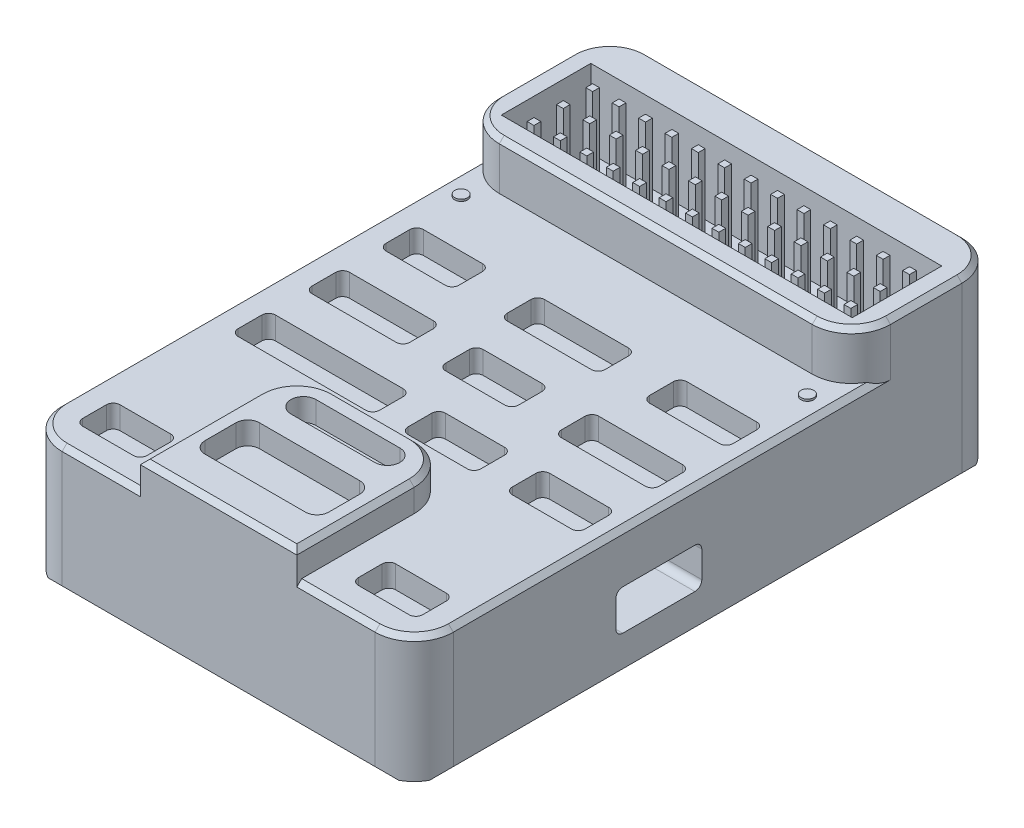
SolidWorks part; units mm, degrees
ref_plane "前视基准面" through (0, 0, 0) normal (0, 0, 1) x (1, 0, 0)
ref_plane "上视基准面" through (0, 0, 0) normal (0, 1, 0) x (1, 0, 0)
ref_plane "右视基准面" through (0, 0, 0) normal (1, 0, 0) x (0, 0, -1)
other "Configuration Table"
sketch "草图1" plane through (0, 0, 0) normal (0, 1, 0) x (1, 0, 0)
  line L0 (0, 0) -> (0, 21.7464) construction
  line L1 (20, 0) -> (-20, 0)
  line L2 (-20, 0) -> (-20, 60)
  line L3 (-20, 60) -> (20, 60)
  line L4 (20, 0) -> (20, 60)
  point P9 (0, 0)
  point P10 (0, 60)
  dimension "D1" = 40
  dimension "D2" = 60
extrude "凸台-拉伸1" add sketch "草图1" along normal blind 17.8
sketch "草图2" plane through (-20, 0, 0) normal (-1, 0, 0) x (0, 0, 1)
  line L0 (-40.8529, 6.1321) -> (-34.8554, 6.1321) construction
  line L1 (-40.8529, 7.8603) -> (-34.8554, 7.8603)
  line L2 (-40.8529, 4.404) -> (-34.8554, 4.404)
  line L3 (-40.8529, 6.1321) -> (-34.8554, 6.1321) construction
  line L4 (-29.4054, 7.757) -> (-20.6215, 7.757)
  line L5 (-29.4054, 7.757) -> (-29.4054, 3.6505)
  line L6 (-29.4054, 3.6505) -> (-20.6215, 3.6505)
  line L7 (-20.6215, 7.757) -> (-20.6215, 3.6505)
  line L8 (-40.8529, 7.3673) -> (-34.8554, 7.3673)
  line L9 (-40.8529, 4.897) -> (-34.8554, 4.897)
  line L10 (-44.7, 17.8) -> (-44.7, 12.9)
  line L11 (-44.7, 12.9) -> (0, 12.9)
  line L12 (0, 17.8) -> (0, 0) construction
  line L14 (-60, 0) -> (0, 0)
  line L15 (0, 0) -> (0, 17.8)
  line L16 (0, 17.8) -> (-60, 17.8)
  line L17 (-60, 17.8) -> (-60, 0)
  line L18 (-60, 0) -> (0, 0)
  line L19 (0, 0) -> (0, 17.8)
  line L20 (0, 17.8) -> (-60, 17.8)
  line L21 (-60, 17.8) -> (-60, 0)
  arc A0 (-40.8529, 7.8603) -> (-40.8529, 4.404) centre (-40.8529, 6.1321) ccw
  arc A1 (-34.8554, 4.404) -> (-34.8554, 7.8603) centre (-34.8554, 6.1321) ccw
  arc A2 (-40.8529, 7.3673) -> (-40.8529, 4.897) centre (-40.8529, 6.1321) ccw
  arc A3 (-34.8554, 4.897) -> (-34.8554, 7.3673) centre (-34.8554, 6.1321) ccw
  point P2 (-37.8541, 6.1321)
  point P9 (-37.8541, 6.1321)
  point P24 (0, 13.395)
  point P28 (0, 0)
  point P29 (-40.8529, 7.3673)
  line M2 (0, 0) -> (0, 17.8)
  line M3 (0, 17.8) -> (-60, 17.8)
  dimension "D1" = 0
  dimension "D2" = 15.3
  dimension "D3" = 4.9
extrude "切除-拉伸1" cut sketch "草图2" against normal through all contours L10 L11 M2 M3 region at (-20, 15.35, -22.35)
extrude "切除-拉伸2" cut sketch "草图2<3>" against normal blind 5 contours L7 L4 L5 L6 region at (-20, 5.7038, -25.0134)
sketch "草图2<3>" plane through (-20, 0, 0) normal (-1, 0, 0) x (0, 0, 1) same geometry as "草图2"
extrude "切除-拉伸3" cut sketch "草图2<4>" against normal blind 1.5 contours L2 A1 L1 A0 A3 L9 A2 L8 region at (-20, 7.7596, -37.8541)
sketch "草图2<4>" plane through (-20, 0, 0) normal (-1, 0, 0) x (0, 0, 1) same geometry as "草图2"
extrude "切除-拉伸4" cut sketch "草图2<5>" against normal blind 4 contours L9 A3 L8 A2 region at (-20, 6.1321, -37.8541)
sketch "草图2<5>" plane through (-20, 0, 0) normal (-1, 0, 0) x (0, 0, 1) same geometry as "草图2"
sketch "草图4" plane through (0, 0, 0) normal (0, 0, 1) x (1, 0, 0)
  line L0 (0, 12.9) -> (0, 0) construction
  line L1 (-8, 12.9) -> (-8, 15.734)
  line L2 (-8, 15.734) -> (8, 15.734)
  line L3 (8, 12.9) -> (8, 15.734)
  line L4 (20, 0) -> (20, 12.9)
  line L5 (20, 12.9) -> (-20, 12.9)
  line L6 (-20, 12.9) -> (-20, 0)
  line L7 (-20, 0) -> (20, 0)
  line L8 (20, 0) -> (20, 12.9)
  line L9 (20, 12.9) -> (-20, 12.9)
  line L10 (-20, 12.9) -> (-20, 0)
  line L11 (-20, 0) -> (20, 0)
  point P11 (0, 15.734)
  line M6 (20, 12.9) -> (-20, 12.9)
  dimension "D2" = 8
  dimension "D3" = 2.834
  dimension "D1" = 0
extrude "凸台-拉伸2" add sketch "草图4" against normal blind 16 contours L3 L2 L1 L9 M6 region at (0, 14.317, 0)
sketch "草图5" plane through (0, 12.9, 0) normal (0, 1, 0) x (1, 0, 0)
  line L0 (0, 44.7) -> (0, 16) construction
  line L1 (-17.3827, 37.6277) -> (-9.9418, 37.6277)
  line L2 (-17.3827, 37.6277) -> (-17.3827, 33.8126)
  line L3 (-17.3827, 33.8126) -> (-9.9418, 33.8126)
  line L4 (-9.9418, 37.6277) -> (-9.9418, 33.8126)
  line L5 (-4.9969, 37.6277) -> (4.9969, 37.6277)
  line L6 (-4.9969, 37.6277) -> (-4.9969, 33.8126)
  line L7 (-4.9969, 33.8126) -> (4.9969, 33.8126)
  line L8 (4.9969, 37.6277) -> (4.9969, 33.8126)
  line L9 (9.5637, 37.6277) -> (18.0938, 37.6277)
  line L10 (9.5637, 37.6277) -> (9.5637, 33.8126)
  line L11 (9.5637, 33.8126) -> (18.0938, 33.8126)
  line L12 (18.0938, 37.6277) -> (18.0938, 33.8126)
  line L13 (-17.3827, 30.0626) -> (-7.3959, 30.0626)
  line L14 (-17.3827, 30.0626) -> (-17.3827, 26.2476)
  line L15 (-17.3827, 26.2476) -> (-7.3959, 26.2476)
  line L16 (-7.3959, 30.0626) -> (-7.3959, 26.2476)
  line L17 (-3.7204, 30.0626) -> (3.7204, 30.0626)
  line L18 (-3.7204, 30.0626) -> (-3.7204, 26.2476)
  line L19 (-3.7204, 26.2476) -> (3.7204, 26.2476)
  line L20 (3.7204, 30.0626) -> (3.7204, 26.2476)
  line L21 (8.1071, 30.0626) -> (18.0938, 30.0626)
  line L22 (8.1071, 30.0626) -> (8.1071, 26.2476)
  line L23 (8.1071, 26.2476) -> (18.0938, 26.2476)
  line L24 (18.0938, 30.0626) -> (18.0938, 26.2476)
  line L25 (-17.3827, 22.4976) -> (-2.924, 22.4976)
  line L26 (-17.3827, 22.4976) -> (-17.3827, 18.6825)
  line L27 (-17.3827, 18.6825) -> (-2.924, 18.6825)
  line L28 (-2.924, 22.4976) -> (-2.924, 18.6825)
  line L29 (0, 22.4976) -> (7.4409, 22.4976)
  line L30 (0, 22.4976) -> (0, 18.6825)
  line L31 (0, 18.6825) -> (7.4409, 18.6825)
  line L32 (7.4409, 22.4976) -> (7.4409, 18.6825)
  line L33 (10.653, 22.4976) -> (18.0938, 22.4976)
  line L34 (10.653, 22.4976) -> (10.653, 18.6825)
  line L35 (10.653, 18.6825) -> (18.0938, 18.6825)
  line L36 (18.0938, 22.4976) -> (18.0938, 18.6825)
  line L37 (10.8069, 6.6036) -> (10.8069, 2.7885)
  line L44 (-8, 0) -> (-8, 16)
  line L45 (-8, 16) -> (8, 16)
  line L46 (8, 16) -> (8, 0)
  line L47 (8, 0) -> (20, 0)
  line L48 (20, 0) -> (20, 44.7)
  line L49 (20, 44.7) -> (-20, 44.7)
  line L50 (-20, 44.7) -> (-20, 0)
  line L51 (-20, 0) -> (-8, 0)
  line L52 (-8, 0) -> (-8, 16)
  line L53 (-8, 16) -> (8, 16)
  line L54 (8, 16) -> (8, 0)
  line L55 (8, 0) -> (20, 0)
  line L56 (20, 0) -> (20, 44.7)
  line L57 (20, 44.7) -> (-20, 44.7)
  line L58 (-20, 44.7) -> (-20, 0)
  line L59 (-20, 0) -> (-8, 0)
  line L62 (-17.3827, 6.6036) -> (-10.8069, 6.6036)
  line L63 (-17.3827, 6.6036) -> (-17.3827, 2.7885)
  line L64 (-17.3827, 2.7885) -> (-10.8069, 2.7885)
  line L65 (-10.8069, 6.6036) -> (-10.8069, 2.7885)
  line L66 (17.3827, 2.7885) -> (10.8069, 2.7885)
  line L67 (17.3827, 6.6036) -> (17.3827, 2.7885)
  line L68 (17.3827, 6.6036) -> (10.8069, 6.6036)
  dimension "D2" = 7.0723
  dimension "D3" = 7.4409
  dimension "D4" = 3.8151
  dimension "D5" = 2.6173
  dimension "D6" = 9.9938
  dimension "D7" = 4.5668
  dimension "D8" = 8.5302
  dimension "D9" = 9.9868
  dimension "D10" = 3.75
  dimension "D11" = 3.75
  dimension "D12" = 14.4587
  dimension "D13" = 2.7885
  dimension "D14" = 2.6173
  dimension "D15" = 6.5757
  dimension "D1" = 0
extrude "切除-拉伸5" cut sketch "草图5" against normal blind 2.3 contours L4 L1 L2 L3 | L0 L5 L6 L7 | L5 L0 L7 L8 | L12 L9 L10 L11 | L17 L0 L19 L20 | L0 L17 L18 L19 | L24 L21 L22 L23 | L36 L33 L34 L35 | L32 L29 L30 L31 | L28 L25 L26 L27 | L65 L62 L63 L64 | L67 L68 L37 L66 | L16 L13 L14 L15 | L15 L16 L13 L14 region at (3.7204, 12.9, -20.59) region at (-1.8602, 12.9, -28.1551) region at (1.8602, 12.9, -28.1551) region at (-2.4984, 12.9, -35.7202) region at (2.4984, 12.9, -35.7202) region at (-13.6622, 12.9, -35.7202) region at (13.8288, 12.9, -35.7202) region at (-12.3893, 12.9, -28.1551) region at (13.1005, 12.9, -28.1551) region at (-10.1533, 12.9, -20.59) region at (14.3734, 12.9, -20.59) region at (14.0948, 12.9, -4.6961) region at (-14.0948, 12.9, -4.6961)
sketch "草图6" plane through (0, 15.734, 0) normal (0, 1, 0) x (1, 0, 0)
  line L0 (0, 16) -> (0, 0) construction
  line L1 (8, 16) -> (-8, 16) construction
  line L2 (-4.2909, 12.9668) -> (4.2909, 12.9668) construction
  line L3 (-4.2909, 14.2476) -> (4.2909, 14.2476)
  line L4 (-4.2909, 11.6859) -> (4.2909, 11.6859)
  line L5 (-8, 0) -> (8, 0) construction
  line L6 (-6.3278, 9.3041) -> (6.3278, 9.3041)
  line L7 (-6.3278, 9.3041) -> (-6.3278, 3.738)
  line L8 (-6.3278, 3.738) -> (6.3278, 3.738)
  line L9 (6.3278, 9.3041) -> (6.3278, 3.738)
  arc A0 (-4.2909, 14.2476) -> (-4.2909, 11.6859) centre (-4.2909, 12.9668) ccw
  arc A1 (4.2909, 11.6859) -> (4.2909, 14.2476) centre (4.2909, 12.9668) ccw
  point P7 (0, 12.9668)
  point P16 (0, 0)
  dimension "D1" = 1.2809
  dimension "D2" = 8.5817
  dimension "D3" = 3.0332
  dimension "D4" = 6.3278
  dimension "D5" = 5.5661
  dimension "D6" = 3.738
extrude "切除-拉伸6" cut sketch "草图6" against normal blind 2.3
mirror "镜向1" about plane through (0, 0, 0) normal (1, 0, 0) of "切除-拉伸2"
chamfer "倒角1" distance 0.5 4 edges at (0, 0, -60) (-20, 0, -30) (0, 0, 0) (20, 0, -30)
fillet "圆角1" radius 4 4 edges at (-20, 9.15, -60) (20, 9.15, -60) (20, 6.7, 0) (-20, 6.7, 0)
fillet "圆角2" radius 4 2 edges at (8, 14.317, -16) (-8, 14.317, -16)
chamfer "倒角10" distance 0.5 angle 45 6 edges at (-8, 15.734, -6) (-6.8284, 15.734, -14.8284) (0, 15.734, -16) (8, 15.734, -6) (6.8284, 15.734, -14.8284) (0, 15.734, 0)
chamfer "倒角11" distance 0.5 6 edges at (12, 12.9, 0) (18.8284, 12.9, -1.1716) (20, 12.9, -24.35) (-12, 12.9, 0) (-18.8284, 12.9, -1.1716) (-20, 12.9, -24.35)
fillet "圆角3" radius 4 2 edges at (20, 15.1, -44.7) (-20, 15.1, -44.7)
chamfer "倒角13" distance 0.5 8 edges at (-18.8284, 17.8, -45.8716) (-20, 17.8, -52.35) (-18.8284, 17.8, -58.8284) (0, 17.8, -60) (18.8284, 17.8, -58.8284) (20, 17.8, -52.35) (18.8284, 17.8, -45.8716) (0, 17.8, -44.7)
sketch "草图9" plane through (0, 17.8, 0) normal (0, 1, 0) x (1, 0, 0)
  line L0 (0, 59.5) -> (0, 45.2) construction
  line L2 (-17.9426, 56) -> (17.9426, 56)
  line L3 (-17.9426, 56) -> (-17.9426, 46.8497)
  line L4 (-19.5, 56) -> (-19.5, 48.7)
  line L5 (-16, 45.2) -> (16, 45.2)
  line L6 (19.5, 48.7) -> (19.5, 56)
  line L7 (16, 59.5) -> (-16, 59.5)
  line L8 (-19.5, 56) -> (-19.5, 48.7)
  line L9 (-16, 45.2) -> (16, 45.2)
  line L10 (19.5, 48.7) -> (19.5, 56)
  line L11 (16, 59.5) -> (-16, 59.5)
  line L12 (-17.9426, 46.8497) -> (17.9426, 46.8497)
  line L13 (17.9426, 56) -> (17.9426, 46.8497)
  arc A4 (-19.5, 48.7) -> (-16, 45.2) centre (-16, 48.7) ccw
  arc A5 (16, 45.2) -> (19.5, 48.7) centre (16, 48.7) ccw
  arc A6 (19.5, 56) -> (16, 59.5) centre (16, 56) ccw
  arc A7 (-16, 59.5) -> (-19.5, 56) centre (-16, 56) ccw
  arc A8 (-19.5, 48.7) -> (-16, 45.2) centre (-16, 48.7) ccw
  arc A9 (16, 45.2) -> (19.5, 48.7) centre (16, 48.7) ccw
  arc A10 (19.5, 56) -> (16, 59.5) centre (16, 56) ccw
  arc A11 (-16, 59.5) -> (-19.5, 56) centre (-16, 56) ccw
  dimension "D2" = 1.6497
  dimension "D3" = 17.9426
  dimension "D4" = 9.1503
  dimension "D1" = 0
extrude "切除-拉伸7" cut sketch "草图9" against normal blind 8 contours L0 L2 L3 L12 | L2 L0 L12 L13 region at (8.9713, 17.8, -51.4249) region at (-8.9713, 17.8, -51.4249)
sketch "草图10" plane through (0, 9.8, 0) normal (0, 1, 0) x (1, 0, 0)
  line L0 (0, 56) -> (0, 46.8497) construction
  line L1 (2.35, 54.7959) -> (3.05, 54.7959)
  line L2 (-0.35, 54.7959) -> (0.35, 54.7959)
  line L3 (-0.35, 54.7959) -> (-0.35, 54.0959)
  line L4 (-17.9426, 46.8497) -> (17.9426, 46.8497)
  line L5 (17.9426, 46.8497) -> (17.9426, 56)
  line L6 (17.9426, 56) -> (-17.9426, 56)
  line L7 (-17.9426, 56) -> (-17.9426, 46.8497)
  line L8 (-17.9426, 46.8497) -> (17.9426, 46.8497)
  line L9 (17.9426, 46.8497) -> (17.9426, 56)
  line L10 (17.9426, 56) -> (-17.9426, 56)
  line L11 (-17.9426, 56) -> (-17.9426, 46.8497)
  line L12 (-0.35, 54.0959) -> (0.35, 54.0959)
  line L13 (0.35, 54.7959) -> (0.35, 54.0959)
  line L14 (3.05, 54.7959) -> (3.05, 54.0959)
  line L15 (2.35, 54.0959) -> (3.05, 54.0959)
  line L16 (2.35, 54.7959) -> (2.35, 54.0959)
  line L17 (5.05, 54.7959) -> (5.75, 54.7959)
  line L18 (5.75, 54.7959) -> (5.75, 54.0959)
  line L19 (5.05, 54.0959) -> (5.75, 54.0959)
  line L20 (5.05, 54.7959) -> (5.05, 54.0959)
  line L21 (7.75, 54.7959) -> (8.45, 54.7959)
  line L22 (8.45, 54.7959) -> (8.45, 54.0959)
  line L23 (7.75, 54.0959) -> (8.45, 54.0959)
  line L24 (7.75, 54.7959) -> (7.75, 54.0959)
  line L25 (10.45, 54.7959) -> (11.15, 54.7959)
  line L26 (11.15, 54.7959) -> (11.15, 54.0959)
  line L27 (10.45, 54.0959) -> (11.15, 54.0959)
  line L28 (10.45, 54.7959) -> (10.45, 54.0959)
  line L29 (13.15, 54.7959) -> (13.85, 54.7959)
  line L30 (13.85, 54.7959) -> (13.85, 54.0959)
  line L31 (13.15, 54.0959) -> (13.85, 54.0959)
  line L32 (13.15, 54.7959) -> (13.15, 54.0959)
  line L33 (15.85, 54.7959) -> (16.55, 54.7959)
  line L34 (16.55, 54.7959) -> (16.55, 54.0959)
  line L35 (15.85, 54.0959) -> (16.55, 54.0959)
  line L36 (15.85, 54.7959) -> (15.85, 54.0959)
  line L37 (2.35, 51.7959) -> (3.05, 51.7959)
  line L38 (3.05, 51.7959) -> (3.05, 51.0959)
  line L39 (2.35, 51.0959) -> (3.05, 51.0959)
  line L40 (2.35, 51.7959) -> (2.35, 51.0959)
  line L41 (5.05, 51.7959) -> (5.75, 51.7959)
  line L42 (5.75, 51.7959) -> (5.75, 51.0959)
  line L43 (5.05, 51.0959) -> (5.75, 51.0959)
  line L44 (5.05, 51.7959) -> (5.05, 51.0959)
  line L45 (7.75, 51.7959) -> (8.45, 51.7959)
  line L46 (8.45, 51.7959) -> (8.45, 51.0959)
  line L47 (7.75, 51.0959) -> (8.45, 51.0959)
  line L48 (7.75, 51.7959) -> (7.75, 51.0959)
  line L49 (10.45, 51.7959) -> (11.15, 51.7959)
  line L50 (11.15, 51.7959) -> (11.15, 51.0959)
  line L51 (10.45, 51.0959) -> (11.15, 51.0959)
  line L52 (10.45, 51.7959) -> (10.45, 51.0959)
  line L53 (13.15, 51.7959) -> (13.85, 51.7959)
  line L54 (13.85, 51.7959) -> (13.85, 51.0959)
  line L55 (13.15, 51.0959) -> (13.85, 51.0959)
  line L56 (13.15, 51.7959) -> (13.15, 51.0959)
  line L57 (15.85, 51.7959) -> (16.55, 51.7959)
  line L58 (16.55, 51.7959) -> (16.55, 51.0959)
  line L59 (15.85, 51.0959) -> (16.55, 51.0959)
  line L60 (15.85, 51.7959) -> (15.85, 51.0959)
  line L61 (2.35, 48.7959) -> (3.05, 48.7959)
  line L62 (3.05, 48.7959) -> (3.05, 48.0959)
  line L63 (2.35, 48.0959) -> (3.05, 48.0959)
  line L64 (2.35, 48.7959) -> (2.35, 48.0959)
  line L65 (5.05, 48.7959) -> (5.75, 48.7959)
  line L66 (5.75, 48.7959) -> (5.75, 48.0959)
  line L67 (5.05, 48.0959) -> (5.75, 48.0959)
  line L68 (5.05, 48.7959) -> (5.05, 48.0959)
  line L69 (7.75, 48.7959) -> (8.45, 48.7959)
  line L70 (8.45, 48.7959) -> (8.45, 48.0959)
  line L71 (7.75, 48.0959) -> (8.45, 48.0959)
  line L72 (7.75, 48.7959) -> (7.75, 48.0959)
  line L73 (10.45, 48.7959) -> (11.15, 48.7959)
  line L74 (11.15, 48.7959) -> (11.15, 48.0959)
  line L75 (10.45, 48.0959) -> (11.15, 48.0959)
  line L76 (10.45, 48.7959) -> (10.45, 48.0959)
  line L77 (13.15, 48.7959) -> (13.85, 48.7959)
  line L78 (13.85, 48.7959) -> (13.85, 48.0959)
  line L79 (13.15, 48.0959) -> (13.85, 48.0959)
  line L80 (13.15, 48.7959) -> (13.15, 48.0959)
  line L81 (15.85, 48.7959) -> (16.55, 48.7959)
  line L82 (16.55, 48.7959) -> (16.55, 48.0959)
  line L83 (15.85, 48.0959) -> (16.55, 48.0959)
  line L84 (15.85, 48.7959) -> (15.85, 48.0959)
  line L85 (-0.35, 51.7959) -> (0.35, 51.7959)
  line L86 (0.35, 51.7959) -> (0.35, 51.0959)
  line L87 (-0.35, 51.0959) -> (0.35, 51.0959)
  line L88 (-0.35, 51.7959) -> (-0.35, 51.0959)
  line L89 (-0.35, 48.7959) -> (0.35, 48.7959)
  line L90 (0.35, 48.7959) -> (0.35, 48.0959)
  line L91 (-0.35, 48.0959) -> (0.35, 48.0959)
  line L92 (-0.35, 48.7959) -> (-0.35, 48.0959)
  line L93 (-15.85, 48.7959) -> (-15.85, 48.0959)
  line L94 (-15.85, 48.0959) -> (-16.55, 48.0959)
  line L95 (-16.55, 48.7959) -> (-16.55, 48.0959)
  line L96 (-15.85, 48.7959) -> (-16.55, 48.7959)
  line L97 (-13.15, 48.7959) -> (-13.15, 48.0959)
  line L98 (-13.15, 48.0959) -> (-13.85, 48.0959)
  line L99 (-13.85, 48.7959) -> (-13.85, 48.0959)
  line L100 (-13.15, 48.7959) -> (-13.85, 48.7959)
  line L101 (-10.45, 48.7959) -> (-10.45, 48.0959)
  line L102 (-10.45, 48.0959) -> (-11.15, 48.0959)
  line L103 (-11.15, 48.7959) -> (-11.15, 48.0959)
  line L104 (-10.45, 48.7959) -> (-11.15, 48.7959)
  line L105 (-7.75, 48.7959) -> (-7.75, 48.0959)
  line L106 (-7.75, 48.0959) -> (-8.45, 48.0959)
  line L107 (-8.45, 48.7959) -> (-8.45, 48.0959)
  line L108 (-7.75, 48.7959) -> (-8.45, 48.7959)
  line L109 (-5.05, 48.7959) -> (-5.05, 48.0959)
  line L110 (-5.05, 48.0959) -> (-5.75, 48.0959)
  line L111 (-5.75, 48.7959) -> (-5.75, 48.0959)
  line L112 (-5.05, 48.7959) -> (-5.75, 48.7959)
  line L113 (-2.35, 48.7959) -> (-2.35, 48.0959)
  line L114 (-2.35, 48.0959) -> (-3.05, 48.0959)
  line L115 (-3.05, 48.7959) -> (-3.05, 48.0959)
  line L116 (-2.35, 48.7959) -> (-3.05, 48.7959)
  line L117 (-15.85, 51.7959) -> (-15.85, 51.0959)
  line L118 (-15.85, 51.0959) -> (-16.55, 51.0959)
  line L119 (-16.55, 51.7959) -> (-16.55, 51.0959)
  line L120 (-15.85, 51.7959) -> (-16.55, 51.7959)
  line L121 (-13.15, 51.7959) -> (-13.15, 51.0959)
  line L122 (-13.15, 51.0959) -> (-13.85, 51.0959)
  line L123 (-13.85, 51.7959) -> (-13.85, 51.0959)
  line L124 (-13.15, 51.7959) -> (-13.85, 51.7959)
  line L125 (-10.45, 51.7959) -> (-10.45, 51.0959)
  line L126 (-10.45, 51.0959) -> (-11.15, 51.0959)
  line L127 (-11.15, 51.7959) -> (-11.15, 51.0959)
  line L128 (-10.45, 51.7959) -> (-11.15, 51.7959)
  line L129 (-7.75, 51.7959) -> (-7.75, 51.0959)
  line L130 (-7.75, 51.0959) -> (-8.45, 51.0959)
  line L131 (-8.45, 51.7959) -> (-8.45, 51.0959)
  line L132 (-7.75, 51.7959) -> (-8.45, 51.7959)
  line L133 (-5.05, 51.7959) -> (-5.05, 51.0959)
  line L134 (-5.05, 51.0959) -> (-5.75, 51.0959)
  line L135 (-5.75, 51.7959) -> (-5.75, 51.0959)
  line L136 (-5.05, 51.7959) -> (-5.75, 51.7959)
  line L137 (-2.35, 51.7959) -> (-2.35, 51.0959)
  line L138 (-2.35, 51.0959) -> (-3.05, 51.0959)
  line L139 (-3.05, 51.7959) -> (-3.05, 51.0959)
  line L140 (-2.35, 51.7959) -> (-3.05, 51.7959)
  line L141 (-15.85, 54.7959) -> (-15.85, 54.0959)
  line L142 (-15.85, 54.0959) -> (-16.55, 54.0959)
  line L143 (-16.55, 54.7959) -> (-16.55, 54.0959)
  line L144 (-15.85, 54.7959) -> (-16.55, 54.7959)
  line L145 (-13.15, 54.7959) -> (-13.15, 54.0959)
  line L146 (-13.15, 54.0959) -> (-13.85, 54.0959)
  line L147 (-13.85, 54.7959) -> (-13.85, 54.0959)
  line L148 (-13.15, 54.7959) -> (-13.85, 54.7959)
  line L149 (-10.45, 54.7959) -> (-10.45, 54.0959)
  line L150 (-10.45, 54.0959) -> (-11.15, 54.0959)
  line L151 (-11.15, 54.7959) -> (-11.15, 54.0959)
  line L152 (-10.45, 54.7959) -> (-11.15, 54.7959)
  line L153 (-7.75, 54.7959) -> (-7.75, 54.0959)
  line L154 (-7.75, 54.0959) -> (-8.45, 54.0959)
  line L155 (-8.45, 54.7959) -> (-8.45, 54.0959)
  line L156 (-7.75, 54.7959) -> (-8.45, 54.7959)
  line L157 (-5.05, 54.7959) -> (-5.05, 54.0959)
  line L158 (-5.05, 54.0959) -> (-5.75, 54.0959)
  line L159 (-5.75, 54.7959) -> (-5.75, 54.0959)
  line L160 (-5.05, 54.7959) -> (-5.75, 54.7959)
  line L161 (-2.35, 54.7959) -> (-2.35, 54.0959)
  line L162 (-2.35, 54.0959) -> (-3.05, 54.0959)
  line L163 (-3.05, 54.7959) -> (-3.05, 54.0959)
  line L164 (-2.35, 54.7959) -> (-3.05, 54.7959)
  dimension "D2" = 0.7
  dimension "D3" = 1.2041
  dimension "D1" = 0
  dimension "D4" = 7
  dimension "D5" = 3
extrude "凸台-拉伸5" add sketch "草图10" along normal blind 7.5 contours L141 L144 L143 L142 | L117 L120 L119 L118 | L93 L96 L95 L94 | L97 L100 L99 L98 | L121 L124 L123 L122 | L145 L148 L147 L146 | L149 L152 L151 L150 | L125 L128 L127 L126 | L101 L104 L103 L102 | L105 L108 L107 L106 | L109 L112 L111 L110 | L113 L116 L115 L114 | L137 L140 L139 L138 | L133 L136 L135 L134 | L129 L132 L131 L130 | L157 L160 L159 L158 | L161 L164 L163 L162 | L0 L2 L3 L12 | L2 L0 L12 L13 | L0 L85 L88 L87 | L85 L0 L87 L86 | L0 L89 L92 L91 | L89 L0 L91 L90 | L37 L40 L39 L38 | L1 L16 L15 L14 | L17 L20 L19 L18 | L41 L44 L43 L42 | L69 L72 L71 L70 | L45 L48 L47 L46 | L21 L24 L23 L22 | L25 L28 L27 L26 | L49 L52 L51 L50 | L73 L76 L75 L74 | L77 L80 L79 L78 | L53 L56 L55 L54 | L29 L32 L31 L30 | L33 L36 L35 L34 | L57 L60 L59 L58 | L81 L84 L83 L82 | L155 L154 L153 L156 | L64 L63 L62 L61 | L66 L67 L68 L65 region at (0.175, 9.8, -54.4459) region at (-0.175, 9.8, -54.4459) region at (0.175, 9.8, -51.4459) region at (-0.175, 9.8, -51.4459) region at (-0.175, 9.8, -48.4459) region at (0.175, 9.8, -48.4459) region at (2.7, 9.8, -54.4459) region at (5.4, 9.8, -54.4459) region at (8.1, 9.8, -54.4459) region at (10.8, 9.8, -54.4459) region at (13.5, 9.8, -54.4459) region at (16.2, 9.8, -54.4459) region at (2.7, 9.8, -51.4459) region at (5.4, 9.8, -51.4459) region at (8.1, 9.8, -51.4459) region at (10.8, 9.8, -51.4459) region at (13.5, 9.8, -51.4459) region at (16.2, 9.8, -51.4459) region at (8.1, 9.8, -48.4459) region at (10.8, 9.8, -48.4459) region at (13.5, 9.8, -48.4459) region at (16.2, 9.8, -48.4459) region at (-16.2, 9.8, -48.4459) region at (-13.5, 9.8, -48.4459) region at (-10.8, 9.8, -48.4459) region at (-8.1, 9.8, -48.4459) region at (-5.4, 9.8, -48.4459) region at (-2.7, 9.8, -48.4459) region at (-16.2, 9.8, -51.4459) region at (-13.5, 9.8, -51.4459) region at (-10.8, 9.8, -51.4459) region at (-8.1, 9.8, -51.4459) region at (-5.4, 9.8, -51.4459) region at (-2.7, 9.8, -51.4459) region at (-16.2, 9.8, -54.4459) region at (-13.5, 9.8, -54.4459) region at (-10.8, 9.8, -54.4459) region at (-5.4, 9.8, -54.4459) region at (-2.7, 9.8, -54.4459)
fillet "圆角5" radius 0.7 52 edges at (-17.5, 3.6505, -20.6215) (-17.5, 3.6505, -29.4054) (-17.5, 7.757, -20.6215) (-17.5, 7.757, -29.4054) (17.5, 3.6505, -20.6215) (17.5, 7.757, -29.4054) (17.5, 7.757, -20.6215) (17.5, 3.6505, -29.4054) (18.0938, 11.75, -33.8126) (4.9969, 11.75, -33.8126) (-9.9418, 11.75, -33.8126) (-7.3959, 11.75, -26.2476) (3.7204, 11.75, -26.2476) (18.0938, 11.75, -26.2476) (18.0938, 11.75, -18.6825) (7.4409, 11.75, -18.6825) (-2.924, 11.75, -18.6825) (-10.8069, 11.75, -2.7885) (17.3827, 11.75, -2.7885) (9.5637, 11.75, -33.8126) (8.1071, 11.75, -26.2476) (10.653, 11.75, -18.6825) (0, 11.75, -18.6825) (-3.7204, 11.75, -26.2476) (-4.9969, 11.75, -33.8126) (-17.3827, 11.75, -33.8126) (-17.3827, 11.75, -26.2476) (-17.3827, 11.75, -18.6825) (-17.3827, 11.75, -2.7885) (10.8069, 11.75, -2.7885) (9.5637, 11.75, -37.6277) (-4.9969, 11.75, -37.6277) (-17.3827, 11.75, -37.6277) (-17.3827, 11.75, -30.0626) (-3.7204, 11.75, -30.0626) (8.1071, 11.75, -30.0626) (10.653, 11.75, -22.4976) (0, 11.75, -22.4976) (-17.3827, 11.75, -22.4976) (-17.3827, 11.75, -6.6036) (10.8069, 11.75, -6.6036) (-10.8069, 11.75, -6.6036) (17.3827, 11.75, -6.6036) (18.0938, 11.75, -22.4976) (7.4409, 11.75, -22.4976) (-2.924, 11.75, -22.4976) (-7.3959, 11.75, -30.0626) (3.7204, 11.75, -30.0626) (18.0938, 11.75, -30.0626) (18.0938, 11.75, -37.6277) (4.9969, 11.75, -37.6277) (-9.9418, 11.75, -37.6277)
fillet "圆角6" radius 1.2 4 edges at (6.3278, 14.584, -3.738) (6.3278, 14.584, -9.3041) (-6.3278, 14.584, -9.3041) (-6.3278, 14.584, -3.738)
sketch "草图11" plane through (0, 12.9, 0) normal (0, 1, 0) x (1, 0, 0)
  line L0 (0, 44.7) -> (0, 0.5) construction
  line L1 (-7.5, 0.5) -> (7.5, 0.5) construction
  line L8 (-16, 0.5) -> (-8, 0.5)
  line L9 (-8, 0.5) -> (-8, 12)
  line L10 (-4, 16) -> (4, 16)
  line L11 (8, 12) -> (8, 0.5)
  line L12 (8, 0.5) -> (16, 0.5)
  line L13 (19.5, 4) -> (19.5, 46.7635)
  line L14 (16, 44.7) -> (-16, 44.7)
  line L15 (-19.5, 46.7635) -> (-19.5, 4)
  line L16 (-16, 0.5) -> (-8, 0.5)
  line L17 (-8, 0.5) -> (-8, 12)
  line L18 (-4, 16) -> (4, 16)
  line L19 (8, 12) -> (8, 0.5)
  line L20 (8, 0.5) -> (16, 0.5)
  line L21 (19.5, 4) -> (19.5, 46.7635)
  line L22 (16, 44.7) -> (-16, 44.7)
  line L23 (-19.5, 46.7635) -> (-19.5, 4)
  circle A0 centre (-17.7, 42.5) radius 0.65
  circle A1 centre (17.7, 42.5) radius 0.65
  arc A6 (-19.5, 4) -> (-16, 0.5) centre (-16, 4) ccw
  arc A7 (-4, 16) -> (-8, 12) centre (-4, 12) ccw
  arc A8 (8, 12) -> (4, 16) centre (4, 12) ccw
  arc A9 (16, 0.5) -> (19.5, 4) centre (16, 4) ccw
  arc A10 (16, 44.7) -> (19.5, 46.7635) centre (16, 48.7) ccw
  arc A11 (-19.5, 46.7635) -> (-16, 44.7) centre (-16, 48.7) ccw
  arc A12 (-19.5, 4) -> (-16, 0.5) centre (-16, 4) ccw
  arc A13 (-4, 16) -> (-8, 12) centre (-4, 12) ccw
  arc A14 (8, 12) -> (4, 16) centre (4, 12) ccw
  arc A15 (16, 0.5) -> (19.5, 4) centre (16, 4) ccw
  arc A16 (16, 44.7) -> (19.5, 46.7635) centre (16, 48.7) ccw
  arc A17 (-19.5, 46.7635) -> (-16, 44.7) centre (-16, 48.7) ccw
  point P27 (-12.7278, 16)
  point P29 (-16, 41.9538)
  point P31 (-15.8974, 41.9705)
  point P32 (-15.4971, 42.0738)
  point P33 (-17.8989, 40.5243)
  point P34 (0, 0)
  point P35 (0, 0)
  point P36 (0, 0)
  point P37 (0, 0)
  point P38 (0, 0)
  point P39 (0, 0)
  point P40 (0, 0)
  dimension "D2" = 1.3
  dimension "D3" = 17.7
  dimension "D4" = 2.2
  dimension "D1" = 0
extrude "凸台-拉伸6" add sketch "草图11" along normal blind 0.2 contours A0 | A1 region at (-17.7, 12.9, -42.5) region at (17.7, 12.9, -42.5)
